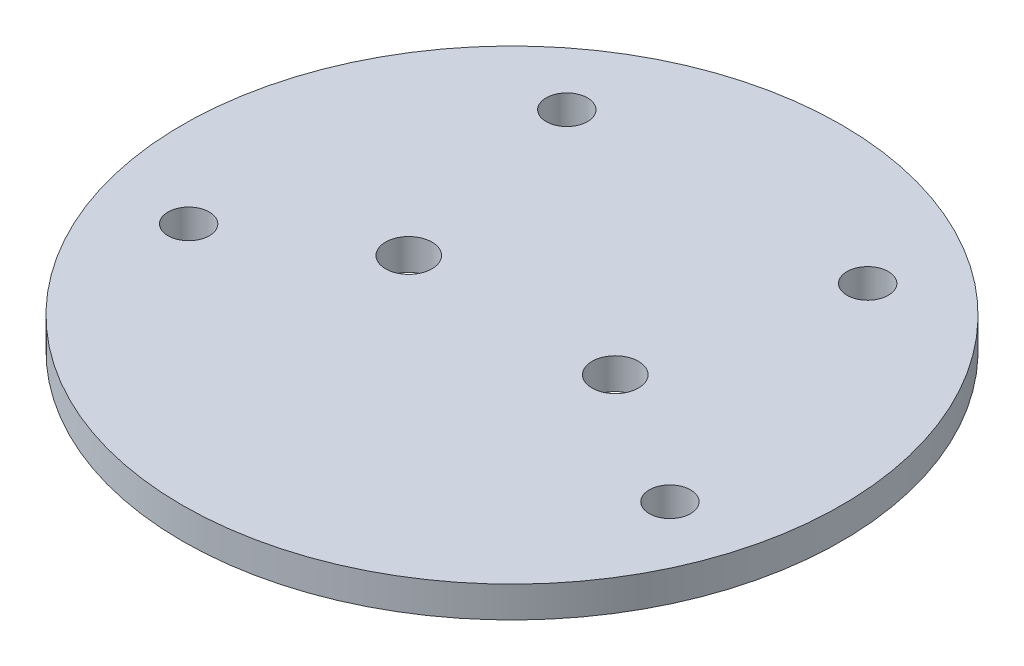
SolidWorks part; units mm, degrees
material "5052-H32"
ref_plane "Front Plane" through (0, 0, 0) normal (0, 0, 1) x (1, 0, 0)
ref_plane "Top Plane" through (0, 0, 0) normal (0, 1, 0) x (1, 0, 0)
ref_plane "Right Plane" through (0, 0, 0) normal (1, 0, 0) x (0, 0, -1)
sketch "Sketch1" plane through (0, 0, 0) normal (0, 1, 0) x (1, 0, 0)
  line L0 (0, 0) -> (-23.1297, 31.5565) construction
  line L1 (0, 0) -> (-41.7254, 0) construction
  line L2 (-37.0005, -12.7186) -> (0, 0) construction
  line L3 (0, -31.6103) -> (0, 47.1695) construction
  circle A0 centre (0, 0) radius 50.673
  circle A3 centre (-15.875, 0) radius 3.5687
  circle A4 centre (15.875, 0) radius 3.5687
  circle A5 centre (-37.0005, -12.7186) radius 3.175
  circle A8 centre (-23.1297, 31.5565) radius 3.175
  circle A9 centre (23.1297, 31.5565) radius 3.175
  circle A10 centre (37.0005, -12.7186) radius 3.175
  dimension "D1" = 101.346
  dimension "D2" = 6.35
  dimension "D3" = 6.35
  dimension "D5" = 15.875
  dimension "D6" = 15.875
  dimension "D4" = 39.1254
  dimension "D7" = 53.76
  dimension "D8" = 39.1254
  dimension "D9" = 18.97
extrude "Boss-Extrude1" add sketch "Sketch1" along normal blind 4.7752
equation "\"allrockets_tube_ID\"= 3.85in"
equation "\"allrockets_tube_OD\"= 4.024in"
equation "\"hole\"= 6.35mm"
equation "\"back_plate_width\"= 28mm"
equation "\"card_spacing\"= 23mm"
equation "\"card_number\"= 7"
equation "\"ToDi\"= 0.05mm"
equation "\"card_diameter\"= 85.86mm"
equation "\"overlap\"= 6.6mm"
equation "\"card_length\"= 68mm"
equation "\"rack_hole_tol\"= 0.35mm"
equation "\"rack_front_width\"= 11.63mm"
equation "\"hole_b_d\"= 39.12541885mm"
equation "\"hole_b_a\"= 18.9721389deg"
equation "\"hole_u_d\"= 39.12541885mm"
equation "\"hole_u_a\"= 53.76090642deg"
equation "\"card_h\"= 61.73mm"
equation "\"sphinx_av\"= 50.292mm"
equation "\"tb_spacing\"= 36mm"
equation "\"D2@Sketch1\"=\"hole\""
equation "\"D4@Sketch1\"=\"hole_u_d\""
equation "\"D7@Sketch1\"=\"hole_u_a\""
equation "\"D8@Sketch1\"=\"hole_b_d\""
equation "\"D9@Sketch1\"=\"hole_b_a\""
